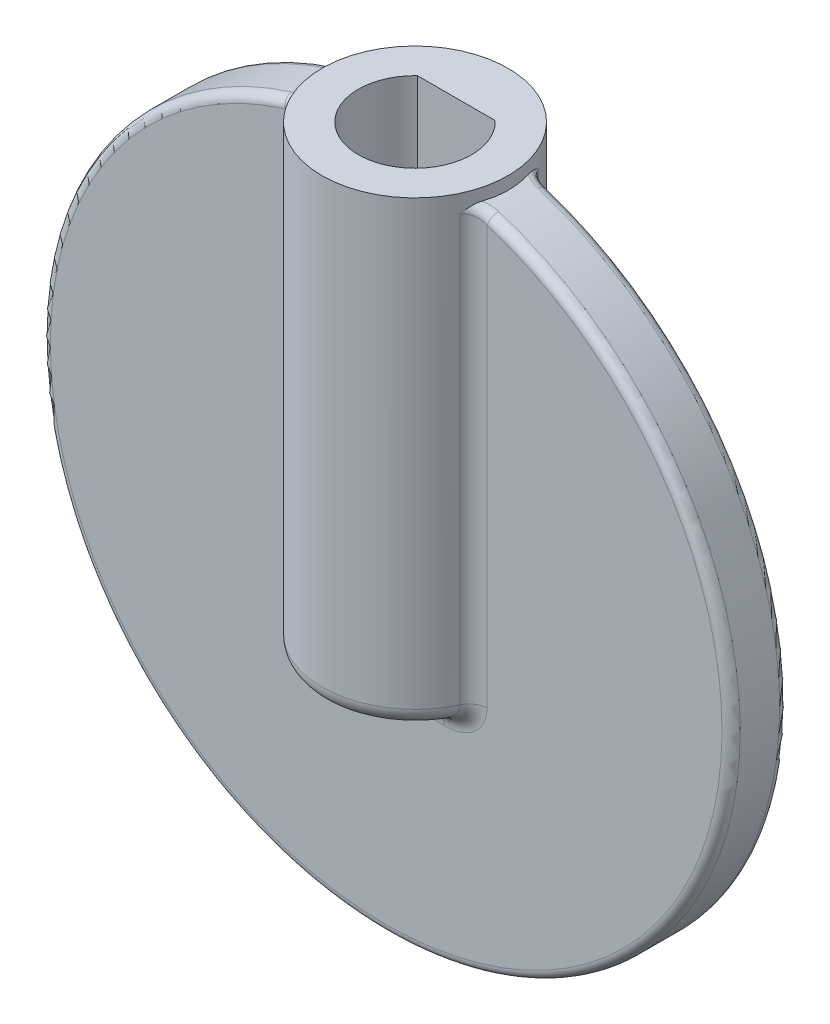
SolidWorks part; units mm, degrees
ref_plane "Front Plane" through (0, 0, 0) normal (0, 0, 1) x (1, 0, 0)
ref_plane "Top Plane" through (0, 0, 0) normal (0, 1, 0) x (1, 0, 0)
ref_plane "Right Plane" through (0, 0, 0) normal (1, 0, 0) x (0, 0, -1)
sketch "Sketch1" plane through (0, 0, 0) normal (0, 1, 0) x (1, 0, 0)
  line L0 (-2.1424, 2.275) -> (2.1424, 2.275) construction
  circle A0 centre (0, 0) radius 5.125
  circle A1 centre (0, 0) radius 3.125 construction
  arc A2 (-2.1424, 2.275) -> (2.1424, 2.275) centre (0, 0) ccw construction
  point P6 (0, -3.125)
  dimension "D1" = 6.25
  dimension "D2" = 2
  dimension "D3" = 5.4
extrude "Boss-Extrude1" add sketch "Sketch1" against normal blind 25.4
ref_plane "Plane1" through (0, 0, 0) normal (0, 1, 0) x (1, 0, 0)
sketch "Sketch2" plane through (0, 0, 0) normal (0, 0, 1) x (1, 0, 0)
  line L0 (5.6375, 0) -> (-5.6375, 0) construction
  circle A0 centre (0, -19) radius 19
  dimension "D1" = 38
extrude "Boss-Extrude2" add sketch "Sketch2" along normal mid plane 3.175
sketch "Sketch3" plane through (0, 0, 0) normal (0, 1, 0) x (1, 0, 0)
  line L0 (-2.1424, 2.275) -> (2.1424, 2.275) construction
  line L1 (-2.1424, 2.275) -> (2.1424, 2.275)
  circle A0 centre (0, 0) radius 3.125 construction
  arc A1 (-2.1424, 2.275) -> (2.1424, 2.275) centre (0, 0) ccw
extrude "Cut-Extrude1" cut sketch "Sketch3" against normal blind 12
fillet "Fillet1" radius 1 8 edges at (0, -25.4, 1.5875) (0, -25.4, -1.5875) (4.8729, -13.0178, 1.5875) (0, -25.4, 5.125) (-4.8729, -13.0178, 1.5875) (0, -25.4, -5.125) (4.8729, -13.0178, -1.5875) (-4.8729, -13.0178, -1.5875)
fillet "Fillet2" radius 0.5 6 edges at (-5.1, -0.6973, -1.6953) (4.9087, -0.645, -1.8216) (-4.9087, -0.645, 1.8216) (5.1, -0.6973, 1.6953) (0, -38, -1.5875) (0, -38, 1.5875)
